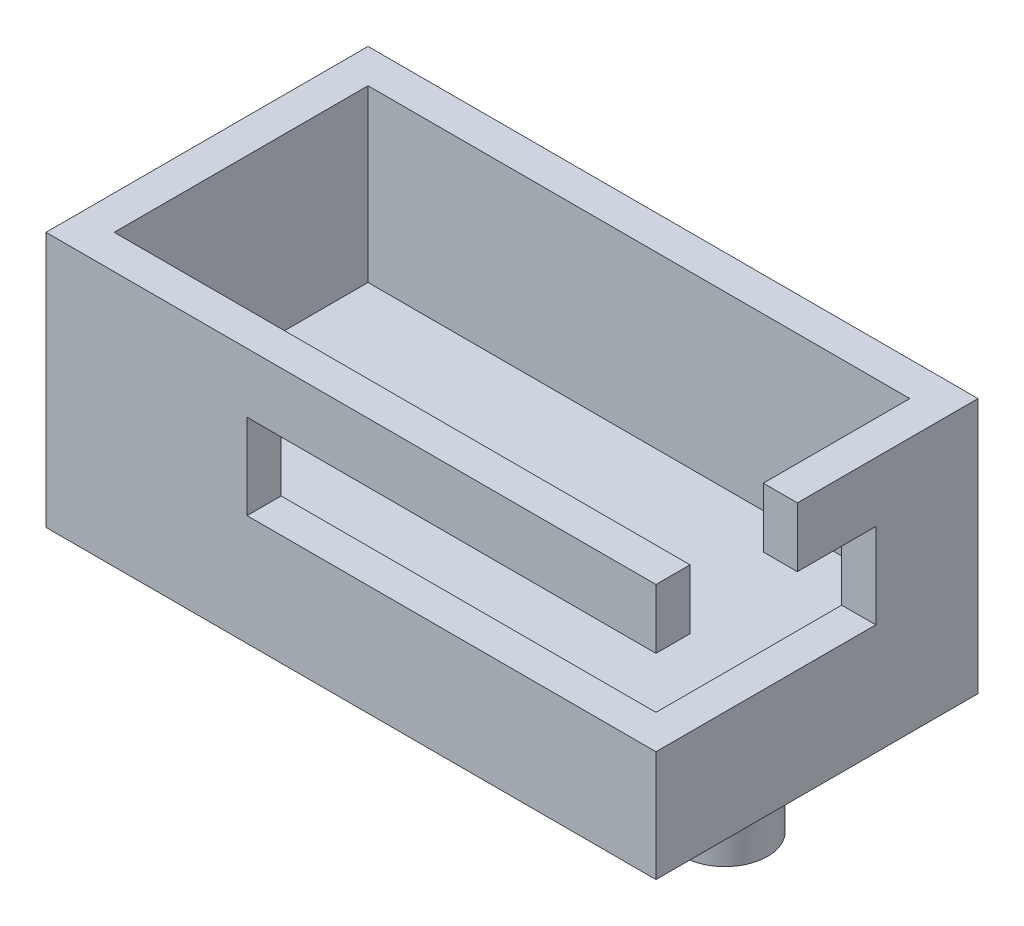
SolidWorks part; units mm, degrees
ref_plane "Front Plane" through (0, 0, 0) normal (0, 0, 1) x (1, 0, 0)
ref_plane "Top Plane" through (0, 0, 0) normal (0, 1, 0) x (1, 0, 0)
ref_plane "Right Plane" through (0, 0, 0) normal (1, 0, 0) x (0, 0, -1)
sketch "Sketch1" plane through (0, 0, 0) normal (0, 1, 0) x (1, 0, 0)
  line L0 (-2, -2) -> (-2, 16.9)
  line L1 (0, 0) -> (31.8, 0)
  line L2 (0, 0) -> (0, 14.9)
  line L3 (0, 14.9) -> (31.8, 14.9)
  line L4 (31.8, 0) -> (31.8, 14.9)
  line L5 (-2, 16.9) -> (33.8, 16.9)
  line L6 (33.8, -2) -> (33.8, 16.9)
  line L7 (-2, -2) -> (33.8, -2)
  dimension "D1" = 14.9
  dimension "D2" = 31.8
  dimension "D3" = 2
extrude "Boss-Extrude1" add sketch "Sketch1" along normal blind 10
extrude "Boss-Extrude2" add sketch "Sketch1<2>" against normal blind 5 contours L0 L7 L6 L5 L4 L1 L2 L3 | L1 L4 L3 L2 region at (-1.5952, 0, -7.45) region at (15.9, 0, -7.45)
sketch "Sketch1<2>" plane through (0, 0, 0) normal (0, 1, 0) x (1, 0, 0) same geometry as "Sketch1"
sketch "Sketch2" plane through (0, 0, 2) normal (0, 0, 1) x (1, 0, 0)
  line L0 (33.8, 10) -> (33.8, -5) construction
  line L1 (9.8, 6.5) -> (33.8, 6.5)
  line L2 (9.8, 6.5) -> (9.8, 1.5)
  line L3 (9.8, 1.5) -> (33.8, 1.5)
  line L4 (33.8, 6.5) -> (33.8, 1.5)
  line L5 (-2, -5) -> (33.8, -5) construction
  dimension "D1" = 24
  dimension "D2" = 5
  dimension "D3" = 6.5
extrude "Cut-Extrude1" cut sketch "Sketch2" against normal offset from surface (12.9 mm away) 6 up to face at (15.9, 2.5, -16.9)
sketch "Sketch3" plane through (33.8, 0, 0) normal (1, 0, 0) x (0, 0, -1)
  line L0 (-2, 10) -> (16.9, 10) construction
  line L1 (0, 6.5) -> (6.3, 6.5)
  line L2 (0, 6.5) -> (0, 10)
  line L3 (0, 10) -> (6.3, 10)
  line L4 (6.3, 6.5) -> (6.3, 10)
  dimension "D1" = 6.3
extrude "Cut-Extrude2" cut sketch "Sketch3" against normal up to surface (2 mm away) up to face at (31.8, 4.5, -6.45)
sketch "Sketch4" plane through (0, -5, 0) normal (0, -1, 0) x (1, 0, 0)
  line L0 (15.9, 2) -> (15.9, -16.9) construction
  line L1 (-2, 2) -> (33.8, 2) construction
  line L2 (-2, -16.9) -> (33.8, -16.9) construction
  line L3 (3.4, -7.45) -> (15.9, -7.45) construction
  circle A0 centre (3.4, -7.45) radius 2.5
  circle A1 centre (28.4, -7.45) radius 2.5
  dimension "D1" = 5
  dimension "D2" = 12.5
extrude "Boss-Extrude3" add sketch "Sketch4" along normal blind 5
fillet "Fillet1" radius 0.4 2 edges at (28.4, -5, -4.95) (3.4, -5, -4.95)
